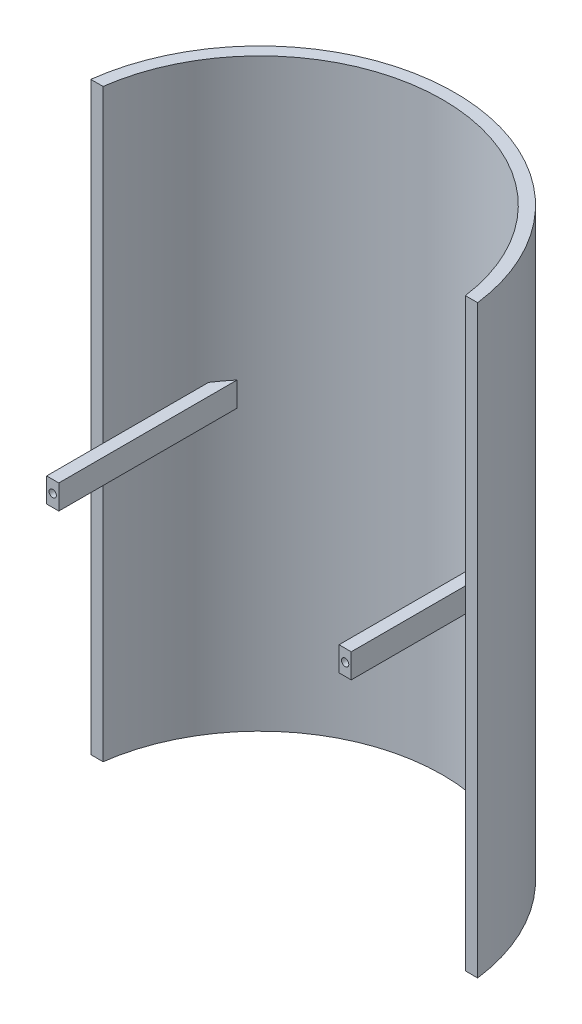
SolidWorks part; units mm, degrees
material "PUR"
ref_plane "Ön Düzlem" through (0, 0, 0) normal (0, 0, 1) x (1, 0, 0)
ref_plane "Üst Düzlem" through (0, 0, 0) normal (0, 1, 0) x (1, 0, 0)
ref_plane "Sağ Düzlem" through (0, 0, 0) normal (1, 0, 0) x (0, 0, -1)
sketch "Çizim1" plane through (0, 0, 0) normal (0, 0, 1) x (1, 0, 0)
  line L1 (-80, 120) -> (80, 120)
  line L2 (-90, 110) -> (-90, -110)
  line L3 (-80, -120) -> (80, -120)
  line L4 (90, 110) -> (90, -110)
  line L5 (-90, 120) -> (90, -120) construction
  line L6 (-90, -120) -> (90, 120) construction
  arc A0 (-90, -110) -> (-80, -120) centre (-80, -110) ccw
  arc A1 (80, -120) -> (90, -110) centre (80, -110) ccw
  arc A2 (80, 120) -> (90, 110) centre (80, 110) cw
  arc A3 (-80, 120) -> (-90, 110) centre (-80, 110) ccw
  point P0 (0, 0)
  dimension "D1" = 10
  dimension "D2" = 220
  dimension "D3" = 160
extrude "Yükseklik-Ekstrüzyon1" add sketch "Çizim1" along normal blind 70
ref_plane "Düzlem1" through (-60, 0, 0) normal (1, 0, 0) x (0, 0, -1)
sketch "Çizim3" plane through (-60, 0, 0) normal (1, 0, 0) x (0, 0, -1)
  line L0 (-5, 5) -> (-105, 5)
  line L1 (-105, 5) -> (-105, -5)
  line L2 (-105, -5) -> (-5, -5)
  line L4 (-5, 5) -> (-5, -5)
  line L7 (0, 110) -> (0, -110) construction
  point P3 (-5, 0)
  dimension "D2" = 10
  dimension "D3" = 100
  dimension "D4" = 5
ref_plane "Düzlem2" through (0, 0, 85) normal (0, 0, 1) x (1, 0, 0)
sketch "Çizim12" plane through (0, 120, 0) normal (0, 1, 0) x (1, 0, 0)
  line L0 (80, 0) -> (-80, 0) construction
  line L1 (90, 0) -> (80, 0) construction
  line L2 (90, -70) -> (90, 0) construction
  line L3 (80, -70) -> (90, -70) construction
  line L4 (80, -70) -> (-80, -70) construction
  line L5 (-90, -70) -> (-80, -70) construction
  line L6 (-80, 0) -> (-90, 0) construction
  line L7 (-90, -70) -> (-90, 0) construction
  line L8 (90, 0) -> (80, 0)
  line L9 (90, -70) -> (90, 0)
  line L10 (80, -70) -> (90, -70)
  line L11 (80, -70) -> (79.3725, -70)
  line L12 (-90, -70) -> (-80, -70)
  line L13 (-80, 0) -> (-90, 0)
  line L14 (-90, -70) -> (-90, 0)
  line L15 (80, 0) -> (-80, 0)
  line L16 (74.3303, -70) -> (-74.3303, -70)
  arc A0 (79.3725, -70) -> (-79.3725, -70) centre (0, -80) ccw
  arc A1 (74.3303, -70) -> (-74.3303, -70) centre (0, -80) ccw
  line M12 (80, 0) -> (-80, 0)
  line M13 (-80, 0) -> (-80, -70)
  line M14 (-80, -70) -> (80, -70)
  line M15 (80, -70) -> (80, 0)
  dimension "D1" = 160
  dimension "D2" = 150
extrude "Kes-Ekstrüzyon11" cut sketch "Çizim12" against normal blind 242 contours A0 L15 M13 M14 | L14 L12 L13 M13 | A1 M14 | A0 M14 M15 M12 | L10 L9 L8 M15 region at (85, 120, 35) region at (62.1036, 120, 17.7862) region at (-62.1036, 120, 17.7862) region at (-85, 120, 35) region at (0, 120, 42.7007)
extrude "Yükseklik-Ekstrüzyon4" add sketch "Çizim3" along normal mid plane 5
sketch "Çizim13" plane through (0, 0, 5) normal (0, 0, -1) x (-1, 0, 0)
  line L4 (62.5, -5) -> (62.5, 5)
  line L5 (62.5, 5) -> (57.5, 5)
  line L6 (57.5, 5) -> (57.5, -5)
  line L7 (57.5, -5) -> (62.5, -5)
  line L8 (62.5, -5) -> (62.5, 5)
  line L9 (62.5, 5) -> (57.5, 5)
  line L10 (57.5, 5) -> (57.5, -5)
  line L11 (57.5, -5) -> (62.5, -5)
  dimension "D1" = 0
extrude "Kes-Ekstrüzyon12" cut sketch "Çizim13" against normal up to surface (19.3785 mm away) up to face at (-60.0336, 0, 27.1909)
sketch "Çizim14" plane through (0, 0, 105) normal (0, 0, 1) x (1, 0, 0)
  line L0 (-60, -38.5) -> (-60, 38.5) construction
  line L1 (-62.5, -5) -> (-57.5, -5) construction
  circle A0 centre (-60, 0) radius 1.5
  dimension "D2" = 3
  dimension "D1" = 5
extrude "Kes-Ekstrüzyon13" cut sketch "Çizim14" against normal blind 27
mirror "Aynalama4" about plane through (0, 0, 0) normal (1, 0, 0) of "Kes-Ekstrüzyon13", "Kes-Ekstrüzyon12", "Yükseklik-Ekstrüzyon4"
